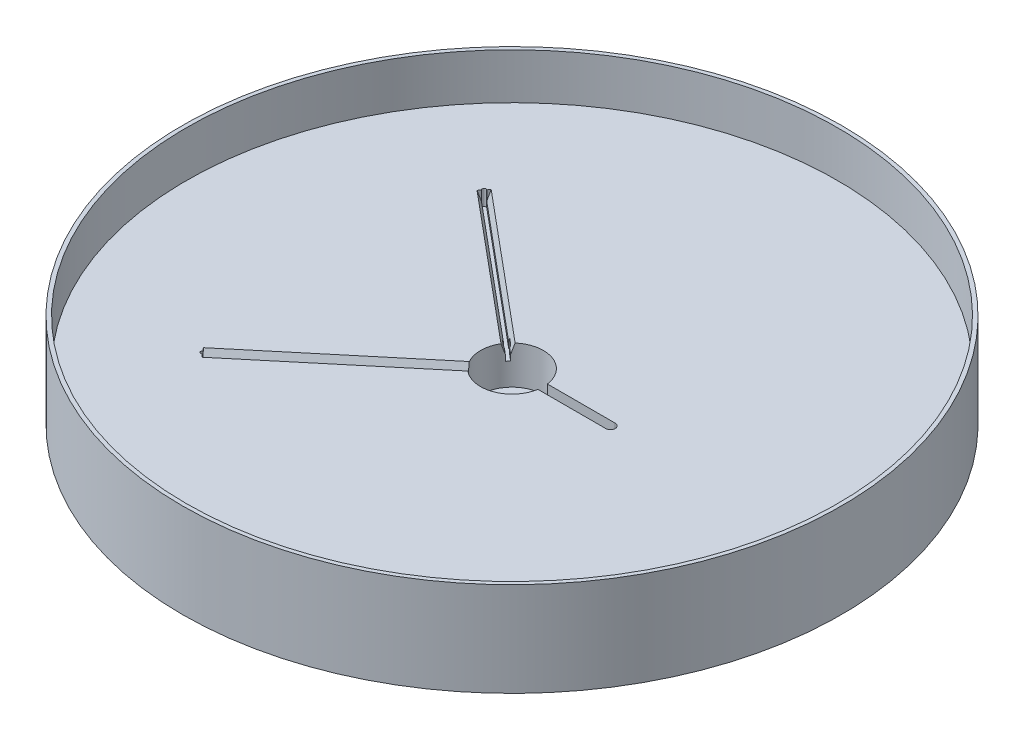
SolidWorks part; units mm, degrees
ref_plane "Front Plane" through (0, 0, 0) normal (0, 0, 1) x (1, 0, 0)
ref_plane "Top Plane" through (0, 0, 0) normal (0, 1, 0) x (1, 0, 0)
ref_plane "Right Plane" through (0, 0, 0) normal (1, 0, 0) x (0, 0, -1)
sketch "Sketch1" plane through (0, 0, 0) normal (0, 1, 0) x (1, 0, 0)
  circle A0 centre (0, 0) radius 266.7
extrude "Boss-Extrude1" add sketch "Sketch1" along normal blind 76.2
sketch "Sketch2" plane through (0, 76.2, 0) normal (0, 1, 0) x (1, 0, 0)
  circle A0 centre (0, 0) radius 263.525
extrude "Cut-Extrude1" cut sketch "Sketch2" against normal blind 37.084
sketch "Sketch3" plane through (0, 39.116, 0) normal (0, 1, 0) x (1, 0, 0)
  circle A0 centre (0, 0) radius 25.4
extrude "Cut-Extrude2" cut sketch "Sketch3" against normal blind 30.988
sketch "Sketch4" plane through (0, 39.116, 0) normal (0, 1, 0) x (1, 0, 0)
  line L0 (3.81, -0.2983) -> (80.01, -0.2983) construction
  line L1 (0, 3.5117) -> (76.2, 3.5117) construction
  line L2 (0, 3.5117) -> (0, -4.1083) construction
  line L3 (0, -4.1083) -> (76.2, -4.1083) construction
  line L4 (76.2, 3.5117) -> (76.2, -4.1083) construction
  line L5 (3.81, 3.5117) -> (80.01, 3.5117)
  line L6 (3.81, -4.1083) -> (80.01, -4.1083)
  line L7 (0, 3.5117) -> (0, -4.1083) construction
  arc A0 (3.81, 3.5117) -> (3.81, -4.1083) centre (3.81, -0.2983) ccw
  arc A1 (80.01, -4.1083) -> (80.01, 3.5117) centre (80.01, -0.2983) ccw
  point P6 (41.91, -0.2983)
extrude "Cut-Extrude3" cut sketch "Sketch4" against normal through all
sketch "Sketch5" plane through (0, 39.116, 0) normal (0, 1, 0) x (1, 0, 0)
  line L0 (0, 0) -> (-39.9134, 33.31) construction
  line L1 (-39.9134, 33.31) -> (-39.9134, -33.31) construction
  line L2 (-39.9134, 0) -> (-42.73, -2.8166) construction
  line L3 (0, 0) -> (-39.9134, 0) construction
  line L4 (-39.9134, 0) -> (-42.73, 2.8166) construction
  line L5 (0, 0) -> (-39.9134, -33.31) construction
  line L6 (0, 0) -> (-136.5075, 113.9234) construction
  line L7 (-0.9765, -1.1701) -> (-137.484, 112.7533)
  line L8 (0.9765, 1.1701) -> (-135.5311, 115.0934)
  line L13 (0, 0) -> (-136.5075, -113.9234) construction
  line L14 (-136.5075, -113.9234) -> (0, 0) construction
  line L15 (-137.484, -112.7533) -> (-0.9765, 1.1701)
  line L16 (-135.5311, -115.0934) -> (0.9765, -1.1701)
  arc A0 (-0.9765, -1.1701) -> (0.9765, 1.1701) centre (0, 0) ccw
  arc A1 (-135.5311, 115.0934) -> (-137.484, 112.7533) centre (-136.5075, 113.9234) ccw
  arc A4 (-137.484, -112.7533) -> (-135.5311, -115.0934) centre (-136.5075, -113.9234) ccw
  arc A5 (0.9765, -1.1701) -> (-0.9765, 1.1701) centre (0, 0) ccw
  point P7 (-68.2538, 56.9617)
  point P24 (-68.2538, -56.9617)
  arc M12 (25.0655, -4.1083) -> (25.1561, 3.5117) centre (0, 0) cw
extrude "Cut-Extrude4" cut sketch "Sketch5" against normal blind 12.7 contours L15 A4 L16 M12 | L7 A1 L8 A0 region at (-78.4582, 39.116, 65.4779)
ref_plane "Plane1" through (-19.4659, 0, -16.2454) normal (0.7678, 0, 0.6407) x (0.6407, 0, -0.7678)
sketch "Sketch6" plane through (-19.4659, 0, -16.2454) normal (0.7678, 0, 0.6407) x (0.6407, 0, -0.7678)
  line L0 (0, 26.416) -> (-4.0671, 39.116)
  line L1 (1.524, 26.416) -> (-1.524, 26.416) construction
  line L2 (-1.524, 39.116) -> (-24.6725, 39.116) construction
  line L3 (-4.0671, 39.116) -> (4.0671, 39.116)
  line L4 (1.524, 39.116) -> (-1.524, 39.116) construction
  line L5 (0, 39.116) -> (0, 26.416) construction
  line L6 (0, 26.416) -> (4.0671, 39.116)
extrude "Cut-Extrude5" cut sketch "Sketch6" against normal blind 152.4 and the other way blind 6.35
ref_plane "Plane2" through (-19.4659, 0, 16.2454) normal (-0.7678, 0, 0.6407) x (0.6407, 0, 0.7678)
sketch "Sketch11" plane through (-19.4659, 0, 16.2454) normal (-0.7678, 0, 0.6407) x (0.6407, 0, 0.7678)
  line L0 (0, 26.416) -> (4.7515, 39.116)
  line L1 (1.524, 26.416) -> (-1.524, 26.416) construction
  line L2 (263.525, 39.116) -> (-263.525, 39.116) construction
  line L3 (4.7515, 39.116) -> (-4.7515, 39.116)
  line L5 (0, 39.4107) -> (0, 26.416) construction
  line L7 (0, 26.416) -> (-4.7515, 39.116)
extrude "Cut-Extrude6" cut sketch "Sketch11" along normal blind 152.4 and the other way blind 6.35
ref_plane "Plane3" through (-24.3412, 0, 20.3141) normal (-0.7678, 0, 0.6407) x (0.6407, 0, 0.7678)
sketch "Sketch12" plane through (-24.3412, 0, 20.3141) normal (-0.7678, 0, 0.6407) x (0.6407, 0, 0.7678)
  line L0 (0, 26.416) -> (0, 31.0485) construction
  line L1 (1.524, 26.416) -> (-1.524, 26.416) construction
  line L2 (2.159, 26.416) -> (-2.159, 26.416) construction
  line L4 (-2.159, 26.416) -> (2.159, 26.416)
  line L7 (-2.159, 26.416) -> (-2.159, 41.4963)
  line L8 (-2.159, 41.4963) -> (2.159, 41.4963)
  line L9 (2.159, 26.416) -> (2.159, 41.4963)
extrude "Cut-Extrude10" cut sketch "Sketch12" along normal blind 6.35
ref_plane "Plane4" through (-24.3412, 0, -20.3141) normal (0.7678, 0, 0.6407) x (0.6407, 0, -0.7678)
sketch "Sketch14" plane through (-24.3412, 0, -20.3141) normal (0.7678, 0, 0.6407) x (0.6407, 0, -0.7678)
  line L0 (-2.159, 39.116) -> (2.159, 39.116) construction
  line L1 (0, 26.416) -> (-2.159, 26.416) construction
  line L2 (1.524, 26.416) -> (-1.524, 26.416) construction
  line L3 (-2.159, 26.416) -> (-2.159, 39.116) construction
  line L4 (2.159, 39.116) -> (2.159, 26.416) construction
  line L5 (2.159, 26.416) -> (0, 26.416) construction
  line L6 (0, 26.416) -> (-0.0449, 26.4266) construction
  line L8 (-2.159, 39.116) -> (2.159, 39.116)
  line L9 (-2.159, 39.116) -> (-2.159, 26.416)
  line L10 (-2.159, 26.416) -> (2.159, 26.416)
  line L11 (2.159, 39.116) -> (2.159, 26.416)
extrude "Cut-Extrude11" cut sketch "Sketch14" against normal blind 6.35
